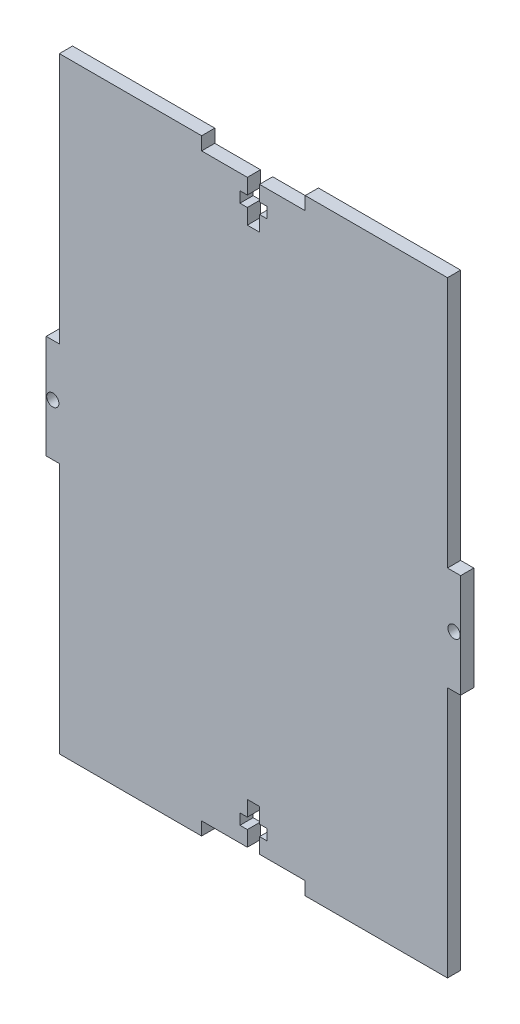
SolidWorks part; units mm, degrees
ref_plane "Front Plane" through (0, 0, 0) normal (0, 0, 1) x (1, 0, 0)
ref_plane "Top Plane" through (0, 0, 0) normal (0, 1, 0) x (1, 0, 0)
ref_plane "Right Plane" through (0, 0, 0) normal (1, 0, 0) x (0, 0, -1)
sketch "Sketch1" plane through (0, 0, 0) normal (0, 0, 1) x (1, 0, 0)
  line L0 (0, 73.175) -> (0, -73.175) construction
  line L1 (-46.825, 73.175) -> (46.825, 73.175)
  line L2 (-46.825, 73.175) -> (-46.825, -73.175)
  line L3 (-46.825, -73.175) -> (46.825, -73.175)
  line L4 (46.825, 73.175) -> (46.825, -73.175)
  line L5 (-46.825, 73.175) -> (46.825, -73.175) construction
  line L6 (-46.825, -73.175) -> (46.825, 73.175) construction
  line L7 (-46.825, 0) -> (46.825, 0) construction
  line L8 (-3.25, -63.7) -> (3.25, -63.7)
  line L9 (12.5, 73.175) -> (-12.5, 73.175)
  line L10 (12.5, 73.175) -> (12.5, 70)
  line L11 (12.5, 70) -> (-12.5, 70)
  line L12 (-12.5, 73.175) -> (-12.5, 70)
  line L13 (12.5, 73.175) -> (-12.5, 70) construction
  line L14 (12.5, 70) -> (-12.5, 73.175) construction
  line L15 (-1.47, 70) -> (1.47, 70)
  line L16 (-1.47, 70) -> (-1.47, 60)
  line L17 (-1.47, 60) -> (1.47, 60)
  line L18 (1.47, 70) -> (1.47, 60)
  line L19 (-1.47, 70) -> (1.47, 60) construction
  line L20 (-1.47, 60) -> (1.47, 70) construction
  line L21 (-3.25, 66.3) -> (3.25, 66.3)
  line L22 (-3.25, 66.3) -> (-3.25, 63.7)
  line L23 (-3.25, 63.7) -> (3.25, 63.7)
  line L24 (3.25, 66.3) -> (3.25, 63.7)
  line L25 (-3.25, 66.3) -> (3.25, 63.7) construction
  line L26 (-3.25, 63.7) -> (3.25, 66.3) construction
  line L27 (3.25, -66.3) -> (3.25, -63.7)
  line L28 (-3.25, -66.3) -> (3.25, -66.3)
  line L29 (-3.25, -66.3) -> (-3.25, -63.7)
  line L30 (-1.47, -60) -> (1.47, -60)
  line L31 (1.47, -70) -> (1.47, -60)
  line L32 (-1.47, -70) -> (1.47, -70)
  line L33 (-1.47, -70) -> (-1.47, -60)
  line L34 (12.5, -70) -> (-12.5, -70)
  line L35 (-12.5, -73.175) -> (-12.5, -70)
  line L36 (12.5, -73.175) -> (-12.5, -73.175)
  line L37 (12.5, -73.175) -> (12.5, -70)
  line L38 (50, -12.5) -> (46.825, -12.5)
  line L39 (-50, 12.5) -> (-46.825, 12.5)
  line L40 (-50, 12.5) -> (-50, -12.5)
  line L41 (-50, -12.5) -> (-46.825, -12.5)
  line L42 (-46.825, 12.5) -> (-46.825, -12.5)
  line L43 (-50, 12.5) -> (-46.825, -12.5) construction
  line L44 (-50, -12.5) -> (-46.825, 12.5) construction
  line L45 (46.825, 12.5) -> (46.825, -12.5)
  line L46 (50, 12.5) -> (46.825, 12.5)
  line L47 (50, 12.5) -> (50, -12.5)
  circle A0 centre (-48.4125, 0) radius 1.47
  circle A1 centre (48.4125, 0) radius 1.47
  point P0 (0, 0)
  point P10 (0, 71.5875)
  point P15 (0, 65)
  point P20 (0, 65)
  point P37 (-48.4125, 0)
  dimension "D11" = 2.94
  dimension "D1" = 146.35
  dimension "D2" = 93.65
  dimension "D3" = 3.175
  dimension "D4" = 10
  dimension "D5" = 2.94
  dimension "D6" = 25
  dimension "D7" = 6.5
  dimension "D8" = 2.6
  dimension "D9" = 6.3
  dimension "D10" = 3.175
extrude "Boss-Extrude1" add sketch "Sketch1" along normal mid plane 3.175 contours L21 L24 L23 L18 L17 L16 L22 L11 L12 L1 L2 L3 L4 L10 | L40 L39 L42 L41 | A0 | L38 L45 L46 L47 | A1 region at (0, 0, 0)
